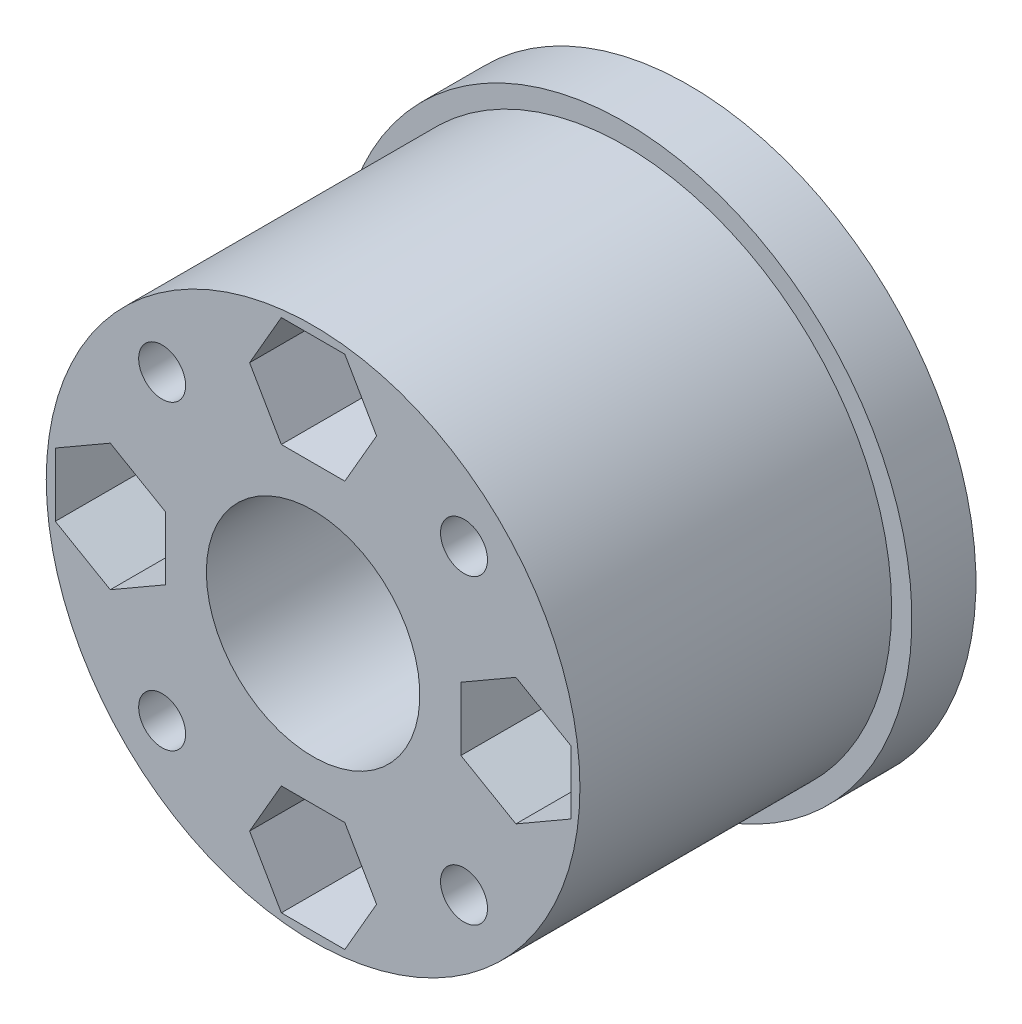
SolidWorks part; units mm, degrees
ref_plane "Front Plane" through (0, 0, 0) normal (0, 0, 1) x (1, 0, 0)
ref_plane "Top Plane" through (0, 0, 0) normal (0, 1, 0) x (1, 0, 0)
ref_plane "Right Plane" through (0, 0, 0) normal (1, 0, 0) x (0, 0, -1)
ref_axis "Z" through (0, 0, 15.48) along (0, 0, -1)
ref_plane "Plane1" through (0, 0, 0) normal (0.7071, 0.7071, 0) x (0, 0, -1)
sketch "Sketch10" plane through (0, 0, 0) normal (0, 1, 0) x (1, 0, 0)
  line L0 (-13.45, 3) -> (-7.5, 3)
  line L1 (0, 38.469) -> (0, 33.6342) construction
  line L2 (0, -15.48) -> (0, 3.88) construction
  line L3 (-13.45, 3) -> (-13.45, 0)
  line L4 (-13.45, 0) -> (-12.5, 0)
  line L5 (-12.5, 0) -> (-12.5, -14.6)
  line L10 (-12.5, -17.2) -> (-11, -17.2) construction
  line L11 (-11, -17.2) -> (-11, -16.2) construction
  line L12 (-11, -16.2) -> (-5, -16.2) construction
  line L14 (-7.5, 3) -> (-7.5, 2)
  line L15 (-7.5, 2) -> (-5, 2)
  line L18 (-5, 2) -> (-5, -14.6)
  line L19 (-12.5, -14.6) -> (-5, -14.6)
  line L20 (-5, -16.2) -> (-5, -14.6)
  line L21 (-12.5, -14.6) -> (-12.5, -17.2)
  dimension "D1" = 25
  dimension "D2" = 26.9
  dimension "D4" = 3
  dimension "D3" = 17.2
  dimension "D8" = 1
  dimension "D9" = 11
  dimension "D11" = 1
  dimension "D12" = 15
  dimension "D5" = 14.6
  dimension "D10" = 10
revolve "Revolve1" add sketch "Sketch10" angle 360 about L1
sketch "Sketch11" plane through (0, 0, 0) normal (0, 0, 1) x (1, 0, 0)
  line L0 (9.5, 0) -> (0, 0) construction
  circle A0 centre (9.5, 0) radius 1.325
  dimension "D2" = 2.65
  dimension "D1" = 9.5
extrude "AttachmentBoltHoles" cut sketch "Sketch11" against normal through all both and the other way through all
sketch "Sketch13" plane through (0, 0, -3) normal (0, 0, -1) x (-1, 0, 0)
  line L0 (-7.0711, 7.0711) -> (0, 0) construction
  line L1 (-9.5, 0) -> (0, 0) construction
  circle A0 centre (-7.0711, 7.0711) radius 1.975
  dimension "D2" = 3.95
  dimension "D1" = 45
  dimension "D3" = 10
extrude "ShaftBoltHead" cut sketch "Sketch13" against normal blind 2.2
sketch "Sketch14" plane through (0, 0, 0) normal (0, 0, 1) x (1, 0, 0)
  circle A0 centre (7.0711, 7.0711) radius 1.1
  dimension "D1" = 2.2
extrude "ShaftBoltThru" cut sketch "Sketch14" along normal through all both and the other way through all
sketch "Sketch12" plane through (0, 0, 14.6) normal (0, 0, 1) x (1, 0, 0)
  line L0 (9.5, 0) -> (0, 0) construction
  line L1 (12.075, -1.4867) -> (12.075, 1.4867)
  line L2 (12.075, 1.4867) -> (9.5, 2.9734)
  line L3 (9.5, 2.9734) -> (6.925, 1.4867)
  line L4 (6.925, 1.4867) -> (6.925, -1.4867)
  line L5 (6.925, -1.4867) -> (9.5, -2.9734)
  line L6 (9.5, -2.9734) -> (12.075, -1.4867)
  circle A0 centre (9.5, 0) radius 2.575 construction
  dimension "D1" = 5.15
extrude "NutHole" cut sketch "Sketch12" against normal offset from surface (12.6 mm away) 5 up to face at (5.0961, 7.0711, -3)
pattern_circular "CirPattern1" count 4 over 360 about axis through (0, 0, 15.48) along (0, 0, -1) of "AttachmentBoltHoles", "NutHole", "ShaftBoltThru", "ShaftBoltHead"
sketch "Sketch15" [suppressed] plane through (0, 0, 0) normal (0, 1, 0) x (1, 0, 0)
  line L0 (-4, -15) -> (-13.45, -15)
  line L1 (-12.5, -15) -> (-5, -15) construction
  line L2 (-13.45, -15) -> (-13.45, -17.6)
  line L3 (0, -10.5706) -> (0, -16.964) construction
  line L4 (-13.45, -17.6) -> (-5.45, -17.6)
  line L5 (-12.5, -17.6) -> (-11, -17.6) construction
  line L6 (-5.45, -17.6) -> (-5.45, -16.6)
  line L7 (-5.45, -16.6) -> (-4, -16.6)
  line L8 (-4, -16.6) -> (-4, -15)
  dimension "D1" = 26.9
  dimension "D2" = 10.9
  dimension "D3" = 1
  dimension "D4" = 8
revolve "Revolve2" [suppressed] add sketch "Sketch15" angle 360 about L3
sketch "Sketch16" [suppressed] plane through (0, 0, 17.6) normal (0, 0, 1) x (1, 0, 0)
  line L0 (7.0711, 7.0711) -> (0, 0) construction
  line L1 (5.3768, 8.7653) -> (4.7567, 6.4509)
  line L2 (4.7567, 6.4509) -> (6.4509, 4.7567)
  line L3 (6.4509, 4.7567) -> (8.7653, 5.3768)
  line L4 (8.7653, 5.3768) -> (9.3854, 7.6912)
  line L5 (9.3854, 7.6912) -> (7.6912, 9.3854)
  line L18 (7.6912, 9.3854) -> (5.3768, 8.7653)
  circle A0 centre (7.0711, 7.0711) radius 2.075 construction
  circle A1 centre (7.0711, 7.0711) radius 1.1
  circle A2 centre (7.0711, 7.0711) radius 1.1 construction
  dimension "D3" = 4.15
  dimension "D2" = 0
extrude "Cut-Extrude1" [suppressed] cut sketch "Sketch16" against normal blind 1.7
sketch "Sketch17" [suppressed] plane through (0, 0, 17.6) normal (0, 0, 1) x (1, 0, 0)
  line L6 (12.075, -1.4867) -> (12.075, 1.4867)
  line L7 (12.075, 1.4867) -> (9.5, 2.9734)
  line L8 (9.5, 2.9734) -> (6.925, 1.4867)
  line L9 (6.925, 1.4867) -> (6.925, -1.4867)
  line L10 (6.925, -1.4867) -> (9.5, -2.9734)
  line L11 (9.5, -2.9734) -> (12.075, -1.4867)
  line L12 (12.075, -1.4867) -> (12.075, 1.4867)
  line L13 (12.075, 1.4867) -> (9.5, 2.9734)
  line L14 (9.5, 2.9734) -> (6.925, 1.4867)
  line L15 (6.925, 1.4867) -> (6.925, -1.4867)
  line L16 (6.925, -1.4867) -> (9.5, -2.9734)
  line L17 (9.5, -2.9734) -> (12.075, -1.4867)
  circle A1 centre (7.0711, 7.0711) radius 1.1
  circle A2 centre (7.0711, 7.0711) radius 1.1
  dimension "D1" = 0
  dimension "D2" = 0
extrude "Cut-Extrude2" [suppressed] cut sketch "Sketch17" against normal through all both and the other way through all
pattern_circular "CirPattern2" [suppressed] count 4 over 360 about axis through (0, 0, 15.48) along (0, 0, -1) of bodies 125
equation "\"BearingOD\"= 32"
equation "\"BearingHeight\"= 4"
equation "\"SeatsOD\"= \"BearingOD\" + 10"
equation "\"RetainingRingThickness\" = 1.30"
equation "\"BearingBaseDistance\"= 17.2 - 2*\"BearingHeight\"  - \"RetainingRingThickness\"*2"
equation "\"WireHarnessHeight\"= 4"
equation "\"OuterWallWidth\"= 6"
equation "\"OverallOD\" = 42"
equation "\"RetaininRingGrooveDiameter\" = 23.9"
equation "\"ShaftLengthAfterFlange\" = 2*\"BearingHeight\" + \"BearingBaseDistance\" + \"RetainingRingThickness\"*2\t'give a retaining ring thickness of extra clearance"
equation "\"RetainingRingGrooveBase\" = \"ShaftLengthAfterFlange\" - \"RetainingRingThickness\"*2"
equation "\"BearingID\" = 25"
equation "\"CoverClearance\" = 1"
equation "\"CoverThickness\" = 1"
equation "\"FlangHeight\" = 3"
equation "\"OuterHousingHeight\" = \"WireHarnessHeight\" + \"BearingHeight\"*2 + \"BearingBaseDistance\""
equation "\"PCBWidth\" = 5"
equation "\"PCBHeight\" = \"OuterHousingHeight\" "
equation "\"PCBThickness\" = 1"
equation "\"NormalDistSidewallPCBToZ\" = (\"OverallOD\"/2) - 1.6\t'radial distance from the z axis to pcb origin on the top/connector side"
equation "\"PCBSidewallCutoutClearance\"= 0.1"
equation "\"OutputHubBoltCircleRadius\"= 8"
equation "\"OutputHubOD\"= 27"
equation "\"StatorWireRadius\"= \"NormalDistSidewallPCBToZ\" - 5.7"
equation "\"MountingHoleRadius\"= (\"OverallOD\"+\"BearingOD\")/4"
equation "\"D1@Sketch10\"=\"BearingID\""
equation "\"BearingInnerRaceOD\"= 26.9"
equation "\"D2@Sketch10\"=\"BearingInnerRaceOD\""
equation "\"D4@Sketch10\"=\"FlangHeight\""
equation "\"D3@Sketch10\"=\"ShaftLengthAfterFlange\""
equation "\"D1@Sketch11\"=round(\"BearingID\"*0.75)/2"
equation "\"D9@Sketch10\"=10.8+0.2"
equation "\"D5@Sketch10\"=\"BearingBaseDistance\" + \"BearingHeight\"*2"
equation "\"D10@Sketch10\"=10"
equation "\"D3@Sketch13\"=\"BearingID\"/2-2.5"
equation "\"D1@Sketch15\"=\"BearingInnerRaceOD\""
equation "\"D2@Sketch15\"=10.9"
